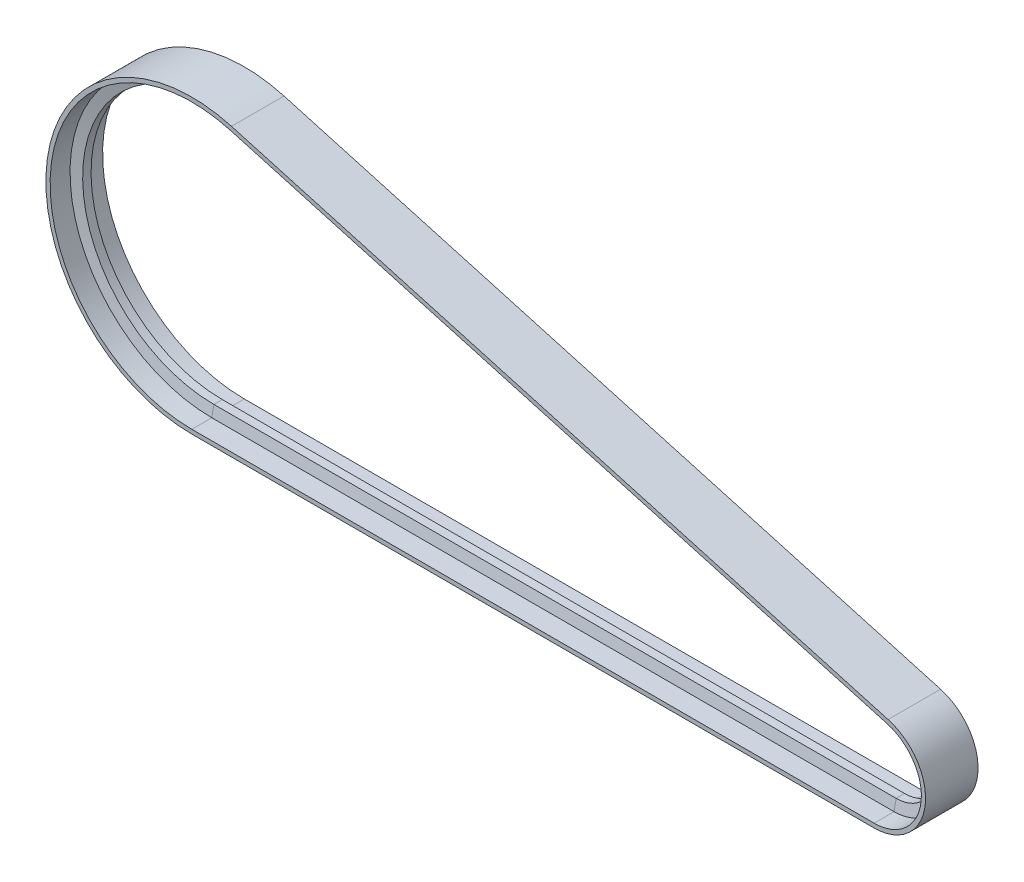
SolidWorks part; units mm, degrees
material "PBT General Purpose"
ref_plane "Front Plane" through (0, 0, 0) normal (0, 0, 1) x (1, 0, 0)
ref_plane "Top Plane" through (0, 0, 0) normal (0, 1, 0) x (1, 0, 0)
ref_plane "Right Plane" through (0, 0, 0) normal (1, 0, 0) x (0, 0, -1)
sketch "Sketch1" plane through (0, 0, 0) normal (0, 0, 1) x (1, 0, 0)
  line L0 (0, -67.5) -> (324.8984, -67.5)
  line L1 (18.3462, 64.959) -> (331.0138, -23.347)
  arc A0 (18.3462, 64.959) -> (0, -67.5) centre (0, 0) ccw
  arc A1 (324.8984, -67.5) -> (331.0138, -23.347) centre (324.8984, -45) ccw
  dimension "D1" = 45
  dimension "D2" = 135
  dimension "D3" = 328
extrude "Extrude-Thin1" add sketch "Sketch1" along normal mid plane 25 thin contours A0 L0 A1 L1 thin type one direction wall 2
sketch "Sketch2" plane through (0, 0, 0) normal (1, 0, 0) x (0, 0, -1)
  line L0 (-3, -67.5) -> (-2, -62.5)
  line L1 (-12.5, -67.5) -> (12.5, -67.5) construction
  line L2 (-2, -62.5) -> (2, -62.5)
  line L3 (2, -62.5) -> (3, -67.5)
  line L4 (0, -62.5) -> (0, -69.5) construction
  line L5 (-12.5, -69.5) -> (12.5, -69.5) construction
  line L6 (3, -67.5) -> (-3, -67.5)
  point P13 (0, -67.5)
  dimension "D1" = 6
  dimension "D2" = 4
  dimension "D3" = 5
sweep "Sweep1" add profiles "Sketch2" path "Sketch1<3>"
sketch "Sketch1<3>" plane through (0, 0, 0) normal (0, 0, 1) x (1, 0, 0) same geometry as "Sketch1"
move or copy body "Body-Move/Copy1" [suppressed] bodies to move or copy 102
